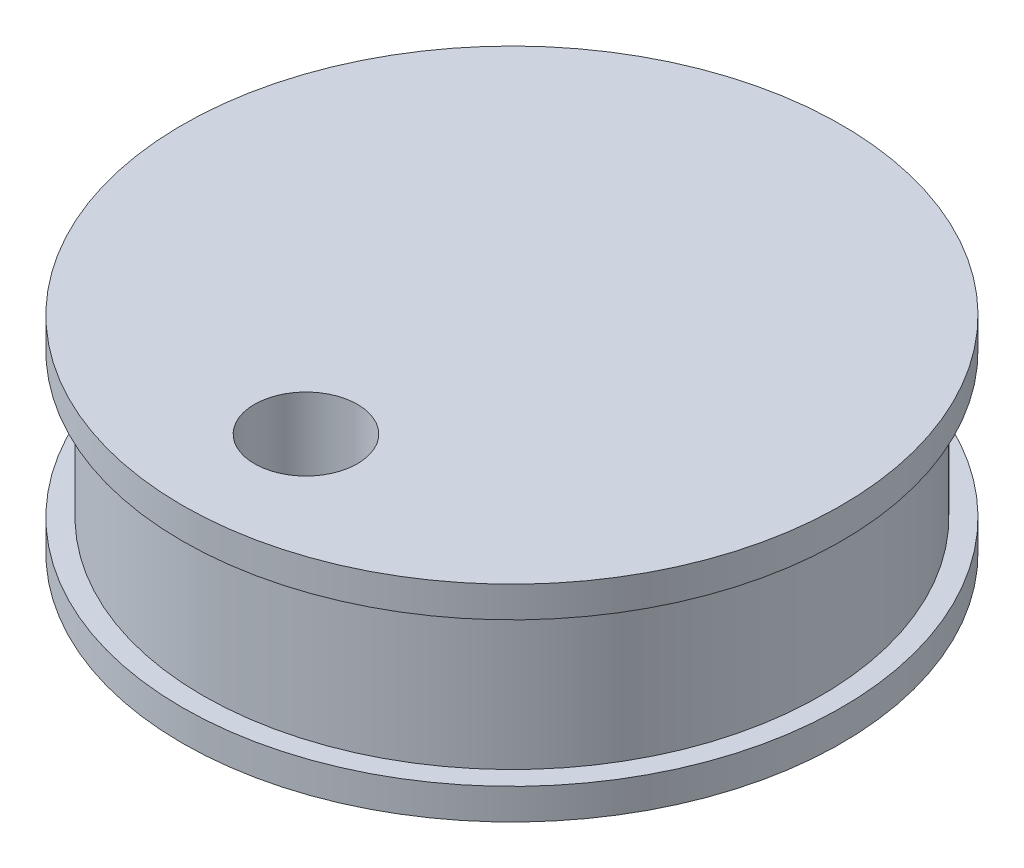
SolidWorks part; units mm, degrees
ref_plane "Front Plane" through (0, 0, 0) normal (0, 0, 1) x (1, 0, 0)
ref_plane "Top Plane" through (0, 0, 0) normal (0, 1, 0) x (1, 0, 0)
ref_plane "Right Plane" through (0, 0, 0) normal (1, 0, 0) x (0, 0, -1)
sketch "Sketch3" plane through (0, 0, 0) normal (0, 0, 1) x (1, 0, 0)
  line L0 (30.48, -1.3614) -> (50.8, -1.3614)
  line L1 (50.8, -1.3614) -> (50.8, 0.5436)
  line L2 (50.8, 0.5436) -> (49.53, 0.5436)
  line L3 (49.53, 0.5436) -> (49.53, 9.4336)
  line L4 (49.53, 9.4336) -> (50.8, 9.4336)
  line L5 (50.8, 9.4336) -> (50.8, 11.3386)
  line L6 (50.8, 11.3386) -> (30.48, 11.3386)
  line L7 (30.48, 11.3386) -> (30.48, -1.3614)
  dimension "D1" = 20.32
  dimension "D2" = 20.32
  dimension "D3" = 8.89
  dimension "D4" = 12.7
  dimension "D5" = 1.27
  dimension "D6" = 1.905
revolve "Revolve1" add sketch "Sketch3" angle 360 about L7
sketch "Sketch4" plane through (0, 11.3386, 0) normal (0, 1, 0) x (1, 0, 0)
  line L0 (30.48, -1.3284) -> (30.48, -20.32) construction
  line L1 (30.48, -20.32) -> (30.48, 20.32) construction
  line L2 (30.48, 20.32) -> (30.48, 0) construction
  line L3 (30.48, 0) -> (50.8, 0) construction
  line L4 (50.8, 0) -> (10.16, 0) construction
  circle A0 centre (30.48, -12.7) radius 3.175
  circle A1 centre (30.48, 0) radius 20.32 construction
  dimension "D3" = 6.35
  dimension "D1" = 0
  dimension "D2" = 12.7
extrude "Cut-Extrude1" cut sketch "Sketch4" against normal through all
